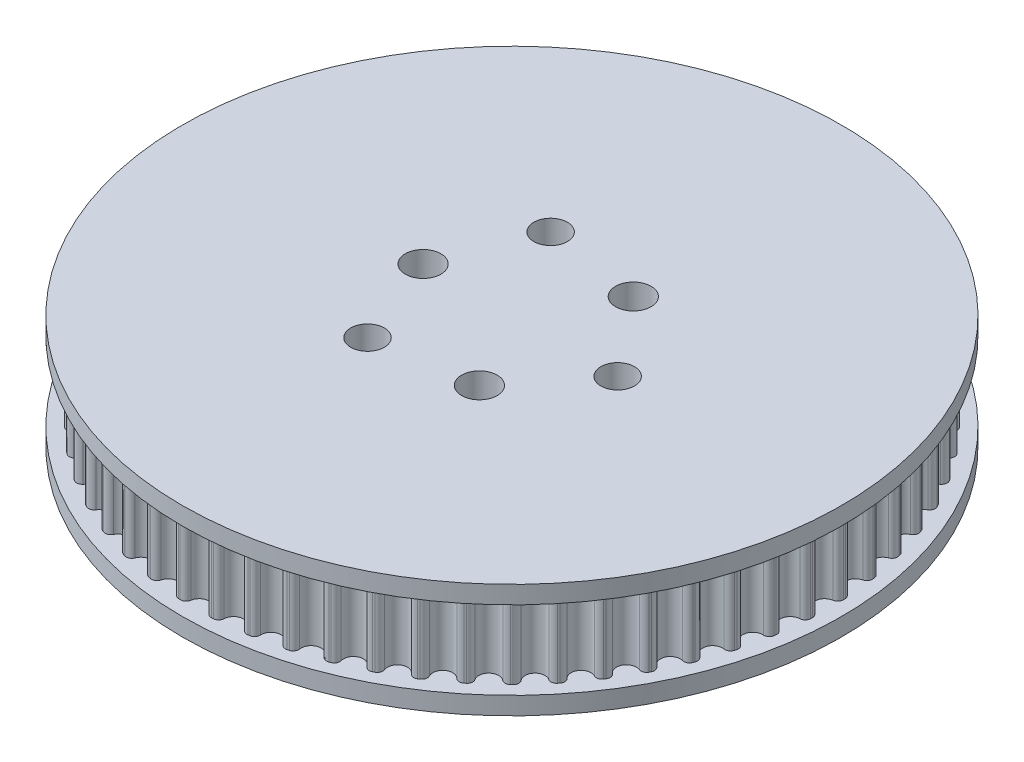
SolidWorks part; units mm, degrees
ref_plane "Front Plane" through (0, 0, 0) normal (0, 0, 1) x (1, 0, 0)
ref_plane "Top Plane" through (0, 0, 0) normal (0, 1, 0) x (1, 0, 0)
ref_plane "Right Plane" through (0, 0, 0) normal (1, 0, 0) x (0, 0, -1)
sketch "Sketch1" plane through (0, 0, 0) normal (0, 1, 0) x (1, 0, 0)
  line L0 (0, 0) -> (0, 28.2667) construction
  line L1 (0, 0) -> (2.9202, 27.7837) construction
  circle A0 centre (0, 0) radius 28.2667 construction
  circle A1 centre (0, 0) radius 27.0467 construction
  circle A2 centre (0, 27.9367) radius 0.89 construction
  circle A5 centre (2.9202, 27.7837) radius 0.89 construction
  arc A6 (0, 27.0467) -> (0.8804, 27.8061) centre (0, 27.9367) ccw
  arc A7 (0.8804, 27.8061) -> (1.3997, 28.2321) centre (1.3749, 27.7327) cw
  arc A8 (1.559, 28.2237) -> (2.031, 27.7458) centre (1.5314, 27.7245) cw
  arc A9 (2.8272, 26.8986) -> (2.031, 27.7458) centre (2.9202, 27.7837) cw
  arc A10 (1.3997, 28.2321) -> (1.559, 28.2237) centre (0, 0) cw
  arc A11 (0, 27.0467) -> (2.8272, 26.8986) centre (0, 0) ccw
  dimension "D1" = 56.5335
  dimension "D3" = 1.78
  dimension "D4" = 0.5
  dimension "D2" = 1.22
  dimension "D5" = 6
extrude "Boss-Extrude1" add sketch "Sketch1" along normal mid plane 7 contours A6 A11 A9 A8 A7 region at (0.001, 0, -0.0192)
ref_axis "Axis1" through (0, 3.3, 0) along (0, -1, 0)
pattern_circular "CirPattern1" count 60 over 360 about axis through (0, 3.3, 0) along (0, -1, 0) of "Boss-Extrude1"
sketch "Sketch2" plane through (0, 0, 0) normal (1, 0, 0) x (0, 0, -1)
  line L10 (0, 3.5) -> (29.4415, 3.5) construction
  line L11 (0, 3.5) -> (0, 5.0875) construction
  line L12 (0, 5.0875) -> (29.4415, 5.0875) construction
  line L15 (29.4415, 3.5) -> (29.4415, 5.0875) construction
  line L20 (0, 3.3) -> (0, -3.3) construction
  line L22 (29.4415, 5.0875) -> (0, 5.0875)
  line L23 (29.4415, 5.0875) -> (29.4415, 3.5)
  line L24 (29.4415, 3.5) -> (0, 3.5)
  line L25 (0, 5.0875) -> (0, 3.5)
  dimension "D1" = 1.5875
  dimension "D2" = 29.4415
  dimension "D3" = 3.5
revolve "Revolve3" add sketch "Sketch2" angle 360 about axis through (0, 3.3, 0) along (0, -1, 0) region at (0, 4.2937, -14.7207)
mirror "Mirror1" about plane through (0, 0, 0) normal (0, 1, 0) of "Revolve3"
sketch "Sketch3" plane through (0, 0, 0) normal (0, -1, 0) x (-1, 0, 0)
  circle A0 centre (0, 0) radius 22.2977
  dimension "D1" = 44.5955
extrude "Cut-Extrude1" [suppressed] cut sketch "Sketch3" against normal through all both and the other way through all
sketch "Sketch4" plane through (0, -5.0875, 0) normal (0, -1, 0) x (-1, 0, 0)
  circle A0 centre (0, 0) radius 12.5
  dimension "D1" = 25
extrude "Cut-Extrude2" cut sketch "Sketch4" against normal blind 4.7625
sketch "Sketch5" plane through (0, 0, 0) normal (0, 1, 0) x (1, 0, 0)
  line L1 (6.6937, -2.75) -> (12.1937, -2.75) construction
  line L2 (6.6937, -2.75) -> (6.6937, 2.75) construction
  line L3 (6.6937, 2.75) -> (12.1937, 2.75) construction
  line L4 (12.1937, -2.75) -> (12.1937, 2.75) construction
  line L5 (6.6937, -2.75) -> (12.1937, 2.75) construction
  line L6 (6.6937, 2.75) -> (12.1937, -2.75) construction
  circle A0 centre (-7.9375, 0) radius 1.5875
  circle A1 centre (9.4437, 0) radius 1.5
  circle A2 centre (0, 0) radius 12.5 construction
  point P11 (0, 0)
  dimension "D1" = 3.175
  dimension "D4" = 3
  dimension "D2" = 7.9375
  dimension "D3" = 5.5
extrude "Cut-Extrude3" cut sketch "Sketch5" against normal through all both and the other way through all
pattern_circular "CirPattern2" count 3 over 360 about axis through (0, 3.3, 0) along (0, -1, 0) of "Cut-Extrude3"
sketch "Sketch6" plane through (0, 0, 0) normal (0, 0, 1) x (1, 0, 0)
  line L1 (-12.5, -5.0875) -> (-14.0875, -5.0875)
  line L2 (-12.5, -5.0875) -> (-12.5, -5.8812)
  line L3 (-12.5, -5.8812) -> (-14.0875, -5.8812)
  line L4 (-14.0875, -5.0875) -> (-14.0875, -5.8812)
  dimension "D1" = 0.7937
  dimension "D2" = 1.5875
revolve "Revolve4" add sketch "Sketch6" angle 360 about axis through (0, 3.3, 0) along (0, -1, 0)
fillet "Fillet1" radius 2.54 1 edges at (0, -5.0875, 14.0875)
equation "\"TEETH_NUM\"= 60"
equation "\"TOOTH_PITCH\"= 3mm"
equation "\"PITCH_LINE_OFFSET\"= .015in"
equation "\"DIAMETER_PER_GROOVE\"= \"OUTSIDE_DIAMETER\" / \"TEETH_NUM\" * 1in"
equation "\"PITCH_DIAMETER\"= ( ( \"TEETH_NUM\" * 3 - 1.31 ) / 3.1415 + .415 ) * 1mm"
equation "\"OUTSIDE_DIAMETER\"= \"PITCH_DIAMETER\" - \"PITCH_LINE_OFFSET\" * 2"
equation "\"D1@Sketch1\"=\"OUTSIDE_DIAMETER\""
equation "\"TOOTH_HEIGHT\"= 1.22mm"
equation "\"D2@Sketch1\"=\"TOOTH_HEIGHT\""
equation "\"TOOTH_DIAMETER\"= 1.78mm"
equation "\"INTERNAL_RADIUS\"= .5mm"
equation "\"D3@Sketch1\"=\"TOOTH_DIAMETER\""
equation "\"D5@Sketch1\"=360 / \"TEETH_NUM\""
equation "\"D4@Sketch1\"=\"INTERNAL_RADIUS\""
equation "\"D1@CirPattern1\"=\"TEETH_NUM\""
equation "\"BELT_GAP\"= 7mm"
equation "\"D2@Sketch2\"=\"PITCH_DIAMETER\"/2+1/32"
equation "\"D3@Sketch2\"=\"BELT_GAP\"/2"
equation "\"D1@Sketch3\"=\"PITCH_DIAMETER\"-.5"
equation "\"D1@Boss-Extrude1\"=\"BELT_GAP\""
